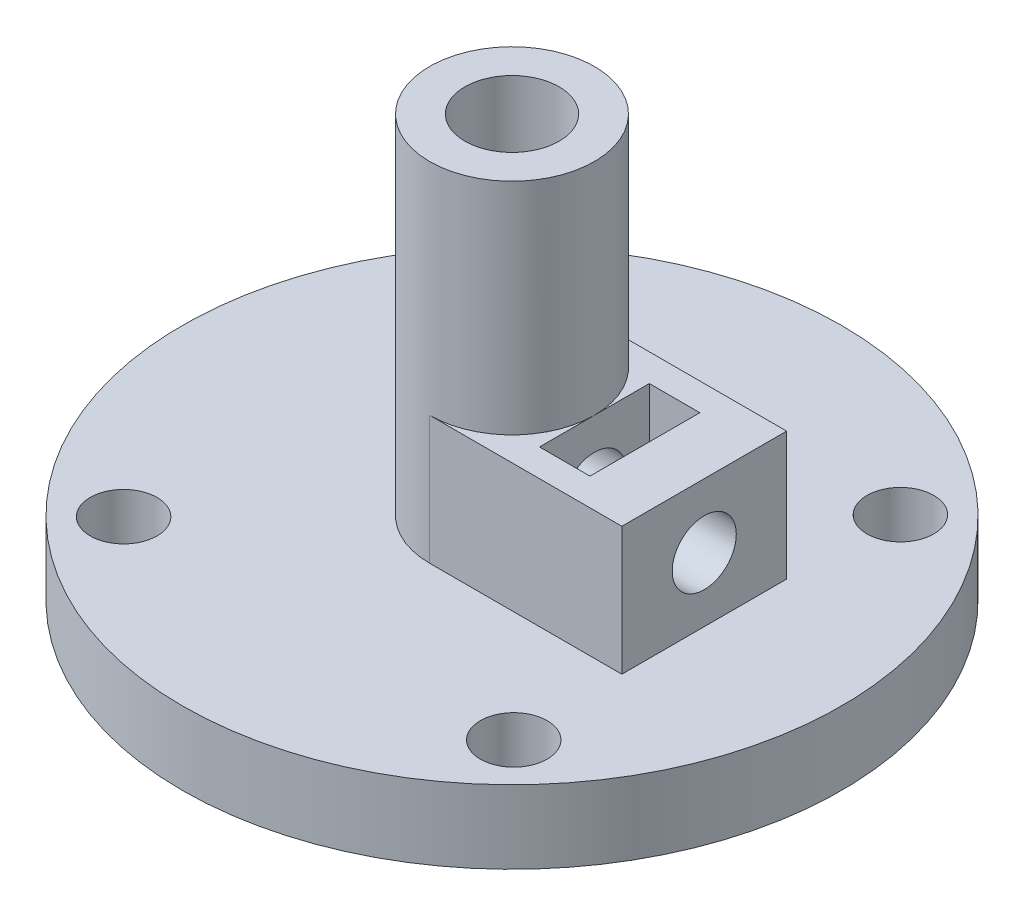
SolidWorks part; units mm, degrees
ref_plane "Front Plane" through (0, 0, 0) normal (0, 0, 1) x (1, 0, 0)
ref_plane "Top Plane" through (0, 0, 0) normal (0, 1, 0) x (1, 0, 0)
ref_plane "Right Plane" through (0, 0, 0) normal (1, 0, 0) x (0, 0, -1)
sketch "Sketch1" plane through (0, 0, 0) normal (0, 1, 0) x (1, 0, 0)
  circle A0 centre (0, 0) radius 18
  dimension "D1" = 36
extrude "Boss-Extrude1" add sketch "Sketch1" along normal blind 4
sketch "Sketch2" plane through (0, 4, 0) normal (0, 1, 0) x (1, 0, 0)
  circle A0 centre (0, 0) radius 15 construction
  circle A1 centre (-10.654, 10.559) radius 1.825
  circle A2 centre (10.559, 10.654) radius 1.825
  circle A3 centre (10.654, -10.559) radius 1.825
  circle A4 centre (0, 0) radius 2.575
  circle A5 centre (-10.559, -10.654) radius 1.825
  dimension "D1" = 30
  dimension "D3" = 3.65
  dimension "D4" = 5.15
  dimension "D2" = 4
extrude "Cut-Extrude1" cut sketch "Sketch2" against normal through all
sketch "Sketch3" plane through (0, 4, 0) normal (0, 1, 0) x (1, 0, 0)
  line L0 (4.5, 0) -> (4.5, 4.5)
  line L1 (0, 4.5) -> (4.5, 4.5)
  line L2 (4.5, 0) -> (4.5, -4.5)
  line L3 (0, -4.5) -> (4.5, -4.5)
  line L4 (4.5, 4.5) -> (10.5, 4.5)
  line L5 (10.5, 4.5) -> (10.5, -4.5)
  line L6 (10.5, -4.5) -> (4.5, -4.5)
  line L7 (4.5, -3) -> (3.7417, -3)
  line L8 (4.5, -3) -> (7.26, -3)
  line L9 (4.5, -3) -> (4.5, 3)
  line L10 (4.5, 3) -> (7.26, 3)
  line L11 (7.26, -3) -> (7.26, 3)
  line L12 (4.5, 3) -> (3.7417, 3)
  circle A0 centre (0, 0) radius 2.575 construction
  circle A1 centre (0, 0) radius 2.575
  circle A2 centre (0, 0) radius 4.5
  circle M3 centre (0, 0) radius 2.575
  dimension "D1" = 9
  dimension "D2" = 6
  dimension "D3" = 3
  dimension "D4" = 3
  dimension "D5" = 2.76
extrude "Boss-Extrude2" add sketch "Sketch3" along normal blind 19 contours A2 M3 region at (3.092, 4, 3.092)
extrude "Boss-Extrude4" add sketch "Sketch3<4>" along normal blind 7 contours A2 L0 L1 | A2 L3 L2 region at (3.4948, 4, -3.4948) region at (3.4948, 4, 3.4948)
sketch "Sketch3<4>" plane through (0, 4, 0) normal (0, 1, 0) x (1, 0, 0) same geometry as "Sketch3"
extrude "Boss-Extrude5" add sketch "Sketch3<5>" along normal blind 7 contours L11 L8 L2 L6 L5 L4 L0 L10 region at (8.2165, 4, 0)
sketch "Sketch3<5>" plane through (0, 4, 0) normal (0, 1, 0) x (1, 0, 0) same geometry as "Sketch3"
sketch "Sketch6" plane through (10.5, 0, 0) normal (1, 0, 0) x (0, 0, -1)
  line L0 (-4.5, 7.5) -> (-3.6199, 7.5) construction
  line L6 (-4.5, 4) -> (4.5, 4)
  line L7 (4.5, 4) -> (4.5, 11)
  line L8 (4.5, 11) -> (-4.5, 11)
  line L9 (-4.5, 11) -> (-4.5, 4)
  line L10 (-4.5, 4) -> (4.5, 4)
  line L11 (4.5, 4) -> (4.5, 11)
  line L12 (4.5, 11) -> (-4.5, 11)
  line L13 (-4.5, 11) -> (-4.5, 4)
  circle A0 centre (0, 7.5) radius 1.75
  point P7 (-4.5, 7.5)
  dimension "D1" = 3.5
  dimension "D2" = 0
extrude "Cut-Extrude2" cut sketch "Sketch6" against normal blind 10 contours A0
